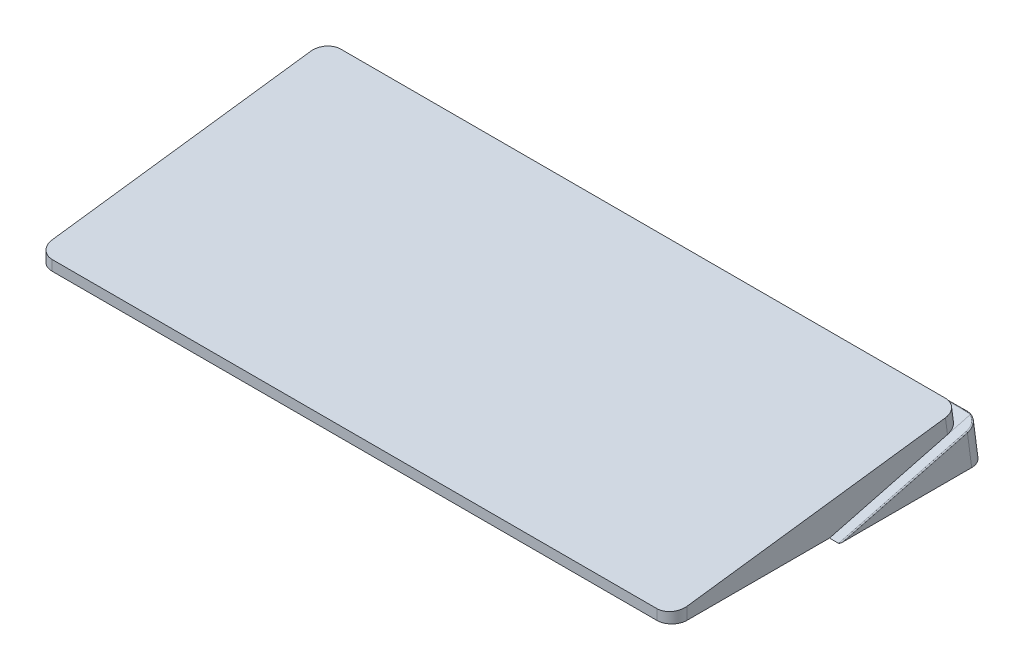
SolidWorks part; units mm, degrees
ref_plane "Front Plane" through (0, 0, 0) normal (0, 0, 1) x (1, 0, 0)
ref_plane "Top Plane" through (0, 0, 0) normal (0, 1, 0) x (1, 0, 0)
ref_plane "Right Plane" through (0, 0, 0) normal (1, 0, 0) x (0, 0, -1)
sketch "Sketch1" plane through (0, 0, 0) normal (0, 1, 0) x (1, 0, 0)
  line L1 (-157.5, 75.665) -> (157.5, 75.665)
  line L2 (-157.5, 75.665) -> (-157.5, -75.665)
  line L3 (-157.5, -75.665) -> (157.5, -75.665)
  line L4 (157.5, 75.665) -> (157.5, -75.665)
  line L5 (-157.5, 75.665) -> (157.5, -75.665) construction
  line L6 (-157.5, -75.665) -> (157.5, 75.665) construction
  point P0 (0, 0)
  dimension "D1" = 315
  dimension "D2" = 151.33
extrude "Boss-Extrude1" add sketch "Sketch1" along normal blind 25
sketch "Sketch2" plane through (0, 0, 0) normal (1, 0, 0) x (0, 0, -1)
  line L0 (-75.665, 5.077) -> (75.665, 25)
  line L1 (-75.665, 25) -> (-75.665, 0) construction
  line L2 (75.665, 25) -> (-75.665, 25)
  line L3 (-75.665, 25) -> (75.665, 25) construction
  line L4 (-75.665, 25) -> (-75.665, 5.077)
  line L5 (75.665, 0) -> (72.4298, 24.5741)
  line L6 (75.665, 25) -> (75.665, 0) construction
  line L7 (75.665, 25) -> (75.665, 0)
  dimension "D1" = 7.5
extrude "Cut-Extrude1" cut sketch "Sketch2" against normal through all both and the other way through all contours L2 L4 L0 | L7 L0 L5 region at (0, 18.359, 25.2217) region at (0, 16.5247, -74.5866)
sketch "Sketch5" plane through (0, 0, 0) normal (1, 0, 0) x (0, 0, -1)
  line L0 (2.55, 0) -> (73.2469, 18.3671)
  line L1 (75.665, 0) -> (-75.665, 0) construction
  line L2 (75.665, 0) -> (72.4298, 24.5741) construction
  line L3 (73.2469, 18.3671) -> (75.665, 0)
  line L4 (75.665, 0) -> (2.55, 0)
  line L5 (71.042, 17.7943) -> (75.665, 0) construction
  dimension "D1" = 2.55
  dimension "D2" = 18.385
extrude "Boss-Extrude2" add sketch "Sketch5" against normal mid plane 325
sketch "Sketch6" plane through (0, 9.7918, -74.3759) normal (0, 0.1305, -0.9914) x (-1, 0, 0)
  line L1 (-162.5, -9.8763) -> (162.5, -9.8763) construction
  line L2 (-62.5, 1.999) -> (62.5, 1.999) construction
  line L3 (-157.5, 8.6493) -> (-162.5, 8.6493) construction
  line L4 (0, -9.8763) -> (0, 14.9099) construction
  line L5 (157.5, 14.9099) -> (-157.5, 14.9099) construction
  line L7 (-157.5, 14.9099) -> (157.5, 14.9099)
  line L8 (-157.5, 14.9099) -> (-157.5, 28.7758)
  line L9 (-157.5, 28.7758) -> (157.5, 28.7758)
  line L10 (157.5, 14.9099) -> (157.5, 28.7758)
  line L14 (-157.5, 14.9099) -> (-157.5, 8.6493)
  line L15 (-157.5, 8.6493) -> (-162.5, 8.6493)
  line L16 (-162.5, 8.6493) -> (-162.5, -9.8763)
  line L17 (-162.5, -9.8763) -> (162.5, -9.8763)
  line L18 (162.5, -9.8763) -> (162.5, 8.6493)
  line L19 (162.5, 8.6493) -> (157.5, 8.6493)
  line L20 (157.5, 8.6493) -> (157.5, 14.9099)
  line L21 (157.5, 14.9099) -> (-157.5, 14.9099)
  line L22 (-157.5, 14.9099) -> (-157.5, 8.6493)
  line L23 (-157.5, 8.6493) -> (-162.5, 8.6493)
  line L24 (-162.5, 8.6493) -> (-162.5, -9.8763)
  line L25 (-162.5, -9.8763) -> (162.5, -9.8763)
  line L26 (162.5, -9.8763) -> (162.5, 8.6493)
  line L27 (162.5, 8.6493) -> (157.5, 8.6493)
  line L28 (157.5, 8.6493) -> (157.5, 14.9099)
  line L29 (157.5, 14.9099) -> (-157.5, 14.9099)
  arc A0 (-62.5, 1.999) -> (62.5, 1.999) centre (0, 446.2156) ccw
  arc A1 (-62.5, 1.999) -> (-157.5, 8.6493) centre (-157.5, -673.2103) ccw
  arc A2 (62.5, 1.999) -> (157.5, 8.6493) centre (157.5, -673.2103) cw
  point P5 (0, -2.3763)
  point P24 (94.0837, 4.6126)
  line M14 (-157.5, 14.9099) -> (-157.5, 8.6493)
  line M20 (157.5, 8.6493) -> (157.5, 14.9099)
  line M21 (157.5, 14.9099) -> (-157.5, 14.9099)
  dimension "D1" = 7.5
  dimension "D3" = 125
  dimension "D2" = 0
extrude "Cut-Extrude4" cut sketch "Sketch6" along direction (0, -0.2515, 0.9679) on the side against the normal blind 5 contours A0 A2 A1 M20 M21 M14 | L8 L7 L10 L9 region at (0, 18.2303, -73.2649)
fillet "Fillet2" [suppressed] radius 0.5
fillet "Fillet1" radius 7.5 6 edges at (-157.5, 2.5385, 75.665) (157.5, 2.5385, 75.665) (-162.5, 9.1836, -74.456) (162.5, 9.1836, -74.456)
sketch "Sketch4" plane through (0, 0, 0) normal (0, 1, 0) x (1, 0, 0)
  line L1 (-160.1297, 68.0505) -> (160.1297, 68.0505)
  line L2 (-160.1297, 68.0505) -> (-160.1297, -68.0505)
  line L3 (-160.1297, -68.0505) -> (160.1297, -68.0505)
  line L4 (160.1297, 68.0505) -> (160.1297, -68.0505)
  line L5 (-160.1297, 68.0505) -> (160.1297, -68.0505) construction
  line L6 (-160.1297, -68.0505) -> (160.1297, 68.0505) construction
  point P0 (0, 0)
extrude "Cut-Extrude3" [suppressed] cut sketch "Sketch4" against normal blind 10 from surface starting at face at (0, 14.5034, 4.0647)
fillet "Fillet3" radius 0.5 9 edges at (-162.5, 8.2334, -34.2412) (-161.1237, 17.5639, -70.1554) (-108.6369, 16.6291, -73.4757) (0, 7.4358, -74.6861) (108.6369, 16.6291, -73.4757) (161.1237, 17.5639, -70.1554) (162.5, 8.2334, -34.2412)
